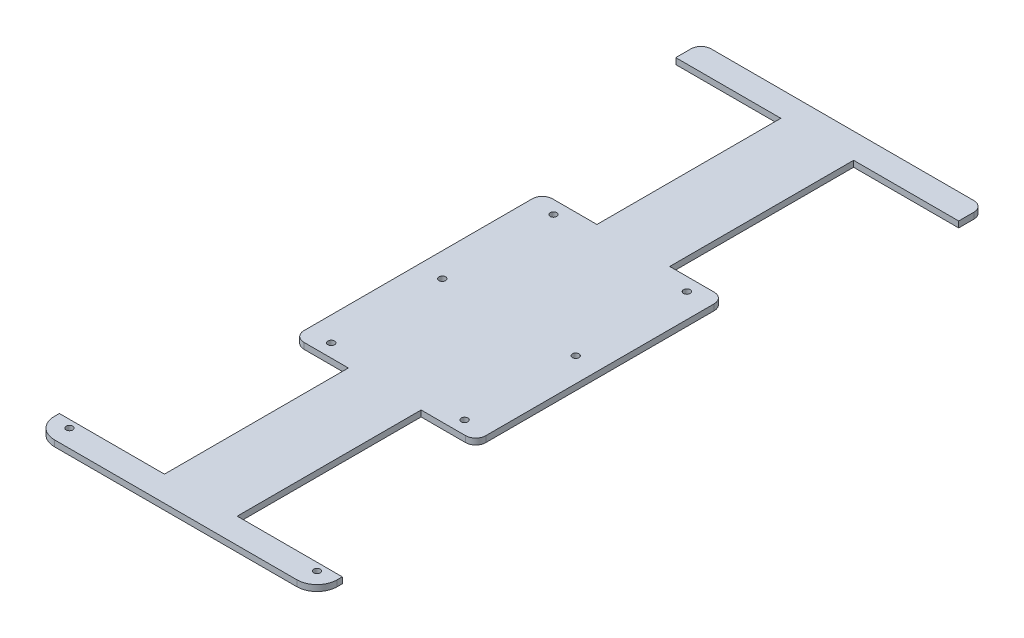
SolidWorks part; units mm, degrees
ref_plane "Front Plane" through (0, 0, 0) normal (0, 0, 1) x (1, 0, 0)
ref_plane "Top Plane" through (0, 0, 0) normal (0, 1, 0) x (1, 0, 0)
ref_plane "Right Plane" through (0, 0, 0) normal (1, 0, 0) x (0, 0, -1)
sketch "Sketch1" plane through (0, 0, 0) normal (0, 1, 0) x (1, 0, 0)
  line L0 (0, 0) -> (140, 0)
  line L1 (0, 0) -> (140, 0) construction
  line L2 (0, 0) -> (0, 330) construction
  line L3 (0, 330) -> (140, 330) construction
  line L4 (140, 0) -> (140, 330) construction
  line L5 (140, 0) -> (140, 12.5)
  line L6 (140, 12.5) -> (88, 12.5)
  line L7 (88, 12.5) -> (88, 103.5)
  line L11 (88, 226.5) -> (88, 317.5)
  line L12 (88, 317.5) -> (140, 317.5)
  line L13 (140, 317.5) -> (140, 330)
  line L14 (140, 330) -> (0, 330)
  line L15 (0, 330) -> (0, 317.5)
  line L16 (0, 317.5) -> (52, 317.5)
  line L17 (52, 317.5) -> (52, 226.5)
  line L21 (52, 103.5) -> (52, 12.5)
  line L22 (52, 12.5) -> (0, 12.5)
  line L23 (0, 12.5) -> (0, 0)
  line L24 (52, 226.5) -> (25, 226.5)
  line L25 (25, 226.5) -> (25, 103.5)
  line L26 (25, 103.5) -> (52, 103.5)
  line L27 (88, 226.5) -> (115, 226.5)
  line L28 (115, 226.5) -> (115, 103.5)
  line L29 (115, 103.5) -> (88, 103.5)
  point P21 (110, 220.4384)
  dimension "D1" = 140
  dimension "D2" = 330
  dimension "D3" = 52
  dimension "D4" = 91
  dimension "D5" = 25
  dimension "D6" = 123
extrude "Boss-Extrude1" add sketch "Sketch1" along normal blind 3
fillet "Fillet1" radius 10 2 edges at (140, 1.5, 0) (0, 1.5, 0)
fillet "Fillet2" radius 5 6 edges at (0, 1.5, -330) (140, 1.5, -330) (115, 1.5, -226.5) (115, 1.5, -103.5) (25, 1.5, -103.5) (25, 1.5, -226.5)
sketch "Sketch2" plane through (0, 3, 0) normal (0, 1, 0) x (1, 0, 0)
  line L2 (37, 220) -> (37, 110) construction
  line L3 (25, 165) -> (37, 165) construction
  line L4 (25, 221.5) -> (25, 108.5) construction
  line L5 (70, 330) -> (70, 0) construction
  line L6 (135, 330) -> (5, 330) construction
  line L7 (10, 0) -> (130, 0) construction
  circle A0 centre (37, 220) radius 1.65
  circle A1 centre (37, 165) radius 1.65
  circle A2 centre (37, 110) radius 1.65
  circle A3 centre (103, 110) radius 1.65
  circle A4 centre (103, 165) radius 1.65
  circle A5 centre (103, 220) radius 1.65
  dimension "D3" = 3.3
  dimension "D1" = 12
  dimension "D2" = 110
extrude "Cut-Extrude1" cut sketch "Sketch2" against normal through all
sketch "Sketch3" plane through (0, 3, 0) normal (0, 1, 0) x (1, 0, 0)
  line L0 (0, 12.5) -> (8.75, 12.5) construction
  line L1 (52, 12.5) -> (0, 12.5) construction
  line L2 (8.75, 12.5) -> (8.75, 8.75) construction
  line L3 (70, 0) -> (70, 57.6288) construction
  line L4 (10, 0) -> (130, 0) construction
  circle A0 centre (8.75, 8.75) radius 1.65
  circle A1 centre (131.25, 8.75) radius 1.65
  dimension "D3" = 3.3
  dimension "D1" = 8.75
  dimension "D2" = 3.75
extrude "Cut-Extrude2" cut sketch "Sketch3" against normal through all
